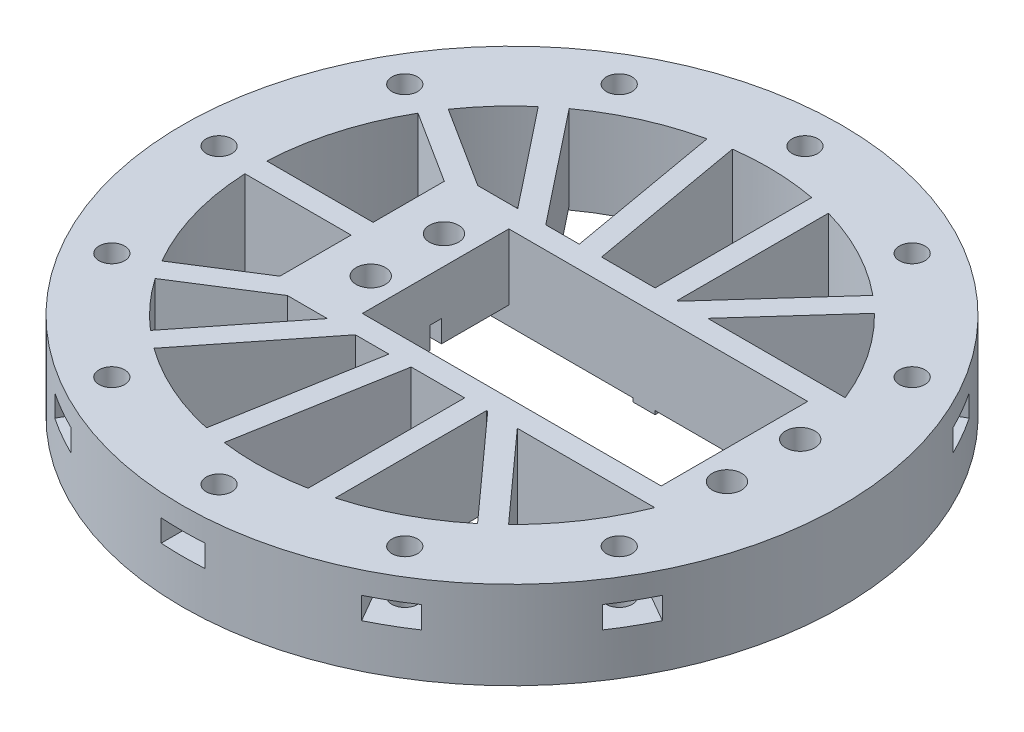
SolidWorks part; units mm, degrees
ref_plane "Front Plane" through (0, 0, 0) normal (0, 0, 1) x (1, 0, 0)
ref_plane "Top Plane" through (0, 0, 0) normal (0, 1, 0) x (1, 0, 0)
ref_plane "Right Plane" through (0, 0, 0) normal (1, 0, 0) x (0, 0, -1)
sketch "Sketch1" plane through (0, 0, 0) normal (0, 1, 0) x (1, 0, 0)
  line L0 (-43.0464, 0) -> (41.9462, 0) construction
  line L1 (0, 43.1152) -> (0, -41.8775) construction
  circle A1 centre (0, 0) radius 45
  dimension "D2" = 90
extrude "Boss-Extrude1" add sketch "Sketch1" along normal blind 12
sketch "Sketch2" plane through (0, 0, 0) normal (0, -1, 0) x (1, 0, 0)
  circle A0 centre (0, 0) radius 35
  dimension "D1" = 70
extrude "Cut-Extrude1" cut sketch "Sketch2" against normal blind 0.5
sketch "Sketch3" plane through (0, 0.5, 0) normal (0, -1, 0) x (1, 0, 0)
  line L0 (35, 0) -> (-35, 0) construction
  line L1 (0, -35) -> (0, 35) construction
  line L3 (37.5324, -10) -> (-17.4676, -10)
  line L4 (37.5324, -10) -> (37.5324, 10)
  line L5 (37.5324, 10) -> (-17.4676, 10)
  line L6 (-17.4676, -10) -> (-17.4676, 10)
  circle A0 centre (0, 0) radius 35 construction
  circle A1 centre (0, 0) radius 35 construction
  dimension "D1" = 20
  dimension "D2" = 55
  dimension "D3" = 10
  dimension "D4" = 37.5324
extrude "Cut-Extrude2" cut sketch "Sketch3" against normal blind 2.5 and the other way up to next
sketch "Sketch4" plane through (0, 3, 0) normal (0, -1, 0) x (1, 0, 0)
  line L0 (37.5324, 0) -> (-17.4676, 0) construction
  line L1 (37.5324, 10) -> (37.5324, -10) construction
  line L2 (-17.4676, 10) -> (-17.4676, -10) construction
  line L3 (0, -10) -> (0, 10) construction
  line L4 (-17.4676, -10) -> (33.541, -10) construction
  line L5 (33.541, 10) -> (-17.4676, 10) construction
  line L7 (30.3722, -10) -> (-10.4278, -10)
  line L8 (30.3722, -10) -> (30.3722, 10)
  line L9 (30.3722, 10) -> (-10.4278, 10)
  line L10 (-10.4278, -10) -> (-10.4278, 10)
  dimension "D1" = 20
  dimension "D2" = 40.8
  dimension "D3" = 30.3722
  dimension "D4" = 10
extrude "Cut-Extrude3" cut sketch "Sketch4" against normal blind 9
sketch "Sketch8" plane through (0, 0.5, 0) normal (0, -1, 0) x (1, 0, 0)
  line L0 (-17.4676, 0) -> (-35, 0) construction
  line L1 (-17.4676, 10) -> (-17.4676, -10) construction
  line L2 (8.0367, 10) -> (8.0367, 34.0648) construction
  line L3 (33.541, 10) -> (-17.4676, 10) construction
  line L4 (8.0367, -10) -> (8.0367, -29.3194) construction
  line L5 (-17.4676, -10) -> (33.541, -10) construction
  line L6 (6.5367, 10) -> (6.5367, 34.3842)
  line L7 (9.5367, 10) -> (9.5367, 33.6757)
  line L8 (9.5367, 10) -> (6.5367, 10)
  line L9 (9.5367, -10) -> (6.5367, -10)
  line L10 (6.5367, -10) -> (6.5367, -34.3842)
  line L11 (9.5367, -10) -> (9.5367, -33.6757)
  line L12 (-17.4676, 1.5) -> (-34.9678, 1.5)
  line L13 (-17.4676, -1.5) -> (-34.9678, -1.5)
  line L14 (-17.4676, 1.5) -> (-17.4676, -1.5)
  arc A0 (33.541, 10) -> (33.541, -10) centre (0, 0) ccw construction
  arc A1 (9.5367, 33.6757) -> (6.5367, 34.3842) centre (7.9531, 33.6757) ccw
  arc A2 (9.5367, -33.6757) -> (6.5367, -34.3842) centre (7.9531, -33.6757) cw
  arc A3 (-34.9678, 1.5) -> (-34.9678, -1.5) centre (-34.9678, 0) ccw
  dimension "D3" = 1.5
  dimension "D1" = 1.5
  dimension "D2" = 1.5
  dimension "D4" = 1.5
extrude "Boss-Extrude2" add sketch "Sketch8" along normal through all
sketch "Sketch15" plane through (0, 0, -1.5) normal (0, 0, -1) x (-1, 0, 0)
  line L0 (34.9678, 0) -> (17.4676, 0.5)
  line L1 (17.4676, 0.5) -> (17.4676, 0)
  line L3 (17.4676, 0) -> (34.9678, 0)
sketch "Sketch16" plane through (0, 3, 0) normal (0, -1, 0) x (1, 0, 0)
  line L0 (-17.4676, 0) -> (37.5324, 0) construction
  line L1 (-17.4676, 10) -> (-17.4676, -10) construction
  line L2 (37.5324, -10) -> (37.5324, 10) construction
  line L3 (30.3722, -0.8) -> (37.5324, -0.8)
  line L4 (-10.4278, -0.8) -> (-17.4676, -0.8)
  line L5 (-10.4278, 10) -> (-10.4278, -10) construction
  line L6 (-10.4278, 0.8) -> (-17.4676, 0.8)
  line L7 (-17.4676, 0.8) -> (-17.4676, -0.8)
  line L8 (-10.4278, 0.8) -> (-10.4278, -0.8)
  line L9 (30.3722, -10) -> (30.3722, 10) construction
  line L10 (30.3722, 0.8) -> (37.5324, 0.8)
  line L11 (37.5324, 0.8) -> (37.5324, -0.8)
  line L12 (30.3722, 0.8) -> (30.3722, -0.8)
  dimension "D1" = 0.8
extrude "Cut-Extrude10" cut sketch "Sketch16" against normal blind 3
sketch "Sketch27" plane through (0, 0, 0) normal (0, -1, 0) x (1, 0, 0)
  line L0 (0, 0) -> (0, -53.17) construction
  line L1 (0, 0) -> (47.7582, -27.5732) construction
  line L3 (31.641, -18.2679) -> (31.641, -21.7321) construction
  line L4 (31.641, -21.7321) -> (34.641, -23.4641) construction
  line L5 (34.641, -23.4641) -> (37.641, -21.7321) construction
  line L6 (37.641, -21.7321) -> (37.641, -18.2679) construction
  line L7 (37.641, -18.2679) -> (34.641, -16.5359) construction
  line L8 (34.641, -16.5359) -> (31.641, -18.2679) construction
  circle A0 centre (0, 0) radius 40 construction
  circle A1 centre (34.641, -20) radius 1.75
  circle A2 centre (0, 0) radius 35 construction
  circle A3 centre (34.641, -20) radius 3 construction
  circle A4 centre (20, -34.641) radius 1.75
  circle A5 centre (0, -40) radius 1.75
  circle A6 centre (-20, -34.641) radius 1.75
  circle A7 centre (-34.641, -20) radius 1.75
  circle A8 centre (-40, 0) radius 1.75
  circle A9 centre (-34.641, 20) radius 1.75
  circle A10 centre (-20, 34.641) radius 1.75
  circle A11 centre (0, 40) radius 1.75
  circle A12 centre (20, 34.641) radius 1.75
  circle A13 centre (34.641, 20) radius 1.75
  circle A15 centre (40, 0) radius 1.75 [skipped]
  point P28 (0, 0)
  point P41 (0, 0)
  dimension "D1" = 80
  dimension "D3" = 3.5
  dimension "D4" = 70
  dimension "D5" = 6
  dimension "D6" = 12
  dimension "D2" = 60
extrude "Cut-Extrude15" cut sketch "Sketch27" against normal through all
ref_plane "Plane1" through (0, 9, 0) normal (0, 1, 0) x (1, 0, 0)
sketch "Sketch28" plane through (0, 9, 0) normal (0, 1, 0) x (1, 0, 0)
  line L0 (0, 0) -> (-54.493, 0) construction
  line L1 (-31.641, 18.2679) -> (-31.641, 21.7321)
  line L2 (-36.5359, 0) -> (-38.2679, 3)
  line L3 (-38.2679, 3) -> (-44.8999, 3)
  line L4 (-31.641, 21.7321) -> (-37.3844, 25.048)
  line L5 (-40.3844, 19.8519) -> (-34.641, 16.5359)
  line L6 (-44.8999, -3) -> (-38.2679, -3)
  line L7 (-38.2679, -3) -> (-36.5359, 0)
  line L8 (-43.4641, 0) -> (-42.5981, -1.5) [skipped]
  line L9 (-41.7321, 3) -> (-42.5981, 1.5) [skipped]
  line L10 (-34.641, 16.5359) -> (-31.641, 18.2679)
  line L11 (-18.2679, 31.641) -> (-16.5359, 34.641)
  line L12 (-16.5359, 34.641) -> (-19.8519, 40.3844)
  line L13 (-25.048, 37.3844) -> (-21.7321, 31.641)
  line L14 (-21.7321, 31.641) -> (-18.2679, 31.641)
  line L15 (0, 36.5359) -> (3, 38.2679)
  line L16 (3, 38.2679) -> (3, 44.8999)
  line L17 (-3, 44.8999) -> (-3, 38.2679)
  line L18 (-3, 38.2679) -> (0, 36.5359)
  line L19 (18.2679, 31.641) -> (21.7321, 31.641)
  line L20 (21.7321, 31.641) -> (25.048, 37.3844)
  line L21 (19.8519, 40.3844) -> (16.5359, 34.641)
  line L22 (16.5359, 34.641) -> (18.2679, 31.641)
  line L23 (31.641, 18.2679) -> (34.641, 16.5359)
  line L24 (34.641, 16.5359) -> (40.3844, 19.8519)
  line L25 (37.3844, 25.048) -> (31.641, 21.7321)
  line L26 (31.641, 21.7321) -> (31.641, 18.2679)
  line L31 (31.641, -18.2679) -> (31.641, -21.7321)
  line L32 (31.641, -21.7321) -> (37.3844, -25.048)
  line L33 (40.3844, -19.8519) -> (34.641, -16.5359)
  line L34 (34.641, -16.5359) -> (31.641, -18.2679)
  line L35 (18.2679, -31.641) -> (16.5359, -34.641)
  line L36 (16.5359, -34.641) -> (19.8519, -40.3844)
  line L37 (25.048, -37.3844) -> (21.7321, -31.641)
  line L38 (21.7321, -31.641) -> (18.2679, -31.641)
  line L39 (0, -36.5359) -> (-3, -38.2679)
  line L40 (-3, -38.2679) -> (-3, -44.8999)
  line L41 (3, -44.8999) -> (3, -38.2679)
  line L42 (3, -38.2679) -> (0, -36.5359)
  line L43 (-18.2679, -31.641) -> (-21.7321, -31.641)
  line L44 (-21.7321, -31.641) -> (-25.048, -37.3844)
  line L45 (-19.8519, -40.3844) -> (-16.5359, -34.641)
  line L46 (-16.5359, -34.641) -> (-18.2679, -31.641)
  line L47 (-31.641, -18.2679) -> (-34.641, -16.5359)
  line L48 (-34.641, -16.5359) -> (-40.3844, -19.8519)
  line L49 (-37.3844, -25.048) -> (-31.641, -21.7321)
  line L50 (-31.641, -21.7321) -> (-31.641, -18.2679)
  line L51 (36.5359, 0) -> (38.2679, -3) [skipped]
  line L52 (38.2679, -3) -> (44.8999, -3) [skipped]
  line L53 (44.8999, 3) -> (38.2679, 3) [skipped]
  line L54 (38.2679, 3) -> (36.5359, 0) [skipped]
  arc A0 (-44.8999, 3) -> (-44.8999, -3) centre (0, 0) ccw
  circle A1 centre (-40, 0) radius 3 construction
  arc A2 (-37.3844, 25.048) -> (-40.3844, 19.8519) centre (0, 0) ccw
  circle A3 centre (-34.641, 20) radius 3 construction
  arc A4 (-19.8519, 40.3844) -> (-25.048, 37.3844) centre (0, 0) ccw
  circle A5 centre (-20, 34.641) radius 3 construction
  arc A6 (3, 44.8999) -> (-3, 44.8999) centre (0, 0) ccw
  circle A7 centre (0, 40) radius 3 construction
  arc A8 (25.048, 37.3844) -> (19.8519, 40.3844) centre (0, 0) ccw
  circle A9 centre (20, 34.641) radius 3 construction
  arc A10 (40.3844, 19.8519) -> (37.3844, 25.048) centre (0, 0) ccw
  circle A11 centre (34.641, 20) radius 3 construction
  arc A14 (37.3844, -25.048) -> (40.3844, -19.8519) centre (0, 0) ccw
  circle A15 centre (34.641, -20) radius 3 construction
  arc A16 (19.8519, -40.3844) -> (25.048, -37.3844) centre (0, 0) ccw
  circle A17 centre (20, -34.641) radius 3 construction
  arc A18 (-3, -44.8999) -> (3, -44.8999) centre (0, 0) ccw
  circle A19 centre (0, -40) radius 3 construction
  arc A20 (-25.048, -37.3844) -> (-19.8519, -40.3844) centre (0, 0) ccw
  circle A21 centre (-20, -34.641) radius 3 construction
  arc A22 (-40.3844, -19.8519) -> (-37.3844, -25.048) centre (0, 0) ccw
  circle A23 centre (-34.641, -20) radius 3 construction
  arc A24 (44.8999, -3) -> (44.8999, 3) centre (0, 0) ccw [skipped]
  circle A25 centre (40, 0) radius 3 construction
  point P94 (0, 0)
  dimension "D1" = 90
  dimension "D2" = 6
  dimension "D3" = 12
extrude "Cut-Extrude17" cut sketch "Sketch28" against normal blind 3
sketch "Sketch29" plane through (0, 0.5, 0) normal (0, -1, 0) x (1, 0, 0)
  line L0 (32.4962, -13) -> (13.7255, -13)
  line L1 (9.5367, -33.6757) -> (9.5367, -10) construction
  line L2 (9.5367, -13) -> (9.5367, -33.6757)
  line L3 (9.5367, -10) -> (33.541, -10) construction
  line L4 (6.5367, -13) -> (-0.7691, -13)
  line L5 (6.5367, -10) -> (6.5367, -34.3842) construction
  line L6 (-20.4676, -11.223) -> (-20.4676, -1.5)
  line L7 (-34.9678, -1.5) -> (-17.4676, -1.5) construction
  line L8 (-20.4676, -1.5) -> (-34.9678, -1.5)
  line L9 (-17.4676, -0.8) -> (-17.4676, -10) construction
  line L10 (32.4962, 13) -> (13.7255, 13)
  line L11 (9.5367, 10) -> (9.5367, 33.6757) construction
  line L12 (9.5367, 13) -> (9.5367, 33.6757)
  line L13 (-7.5493, 34.1761) -> (-3.8154, 13)
  line L14 (6.5367, 13) -> (-0.7691, 13)
  line L15 (6.5367, 34.3842) -> (6.5367, 10) construction
  line L16 (-20.4676, 11.223) -> (-20.4676, 1.5)
  line L17 (-17.4676, 1.5) -> (-34.9678, 1.5) construction
  line L18 (-20.4676, 1.5) -> (-34.9678, 1.5)
  line L19 (6.5367, 13) -> (6.5367, 34.3842)
  line L20 (6.5367, -34.3842) -> (6.5367, -13)
  line L21 (0, 0) -> (-21.7353, -27.4331) construction
  line L22 (-20.5397, -28.3394) -> (-8.3862, -13)
  line L23 (-22.8911, -26.4764) -> (-12.2137, -13)
  line L24 (0, 0) -> (-20.4676, -13) construction
  line L25 (-17.6698, -13) -> (-28.713, -20.0141)
  line L26 (-20.4676, -11.223) -> (-30.3215, -17.4817)
  line L27 (0, 0) -> (-35, 0) construction
  line L28 (-20.4676, 11.223) -> (-30.3215, 17.4817)
  line L29 (-17.6698, 13) -> (-28.713, 20.0141)
  line L30 (-22.8911, 26.4764) -> (-12.2137, 13)
  line L31 (-20.5397, 28.3394) -> (-8.3862, 13)
  line L32 (-12.2137, 13) -> (-17.6698, 13)
  line L33 (0, 0) -> (-6.0777, -34.4683) construction
  line L34 (-4.5949, -34.6971) -> (-0.7691, -13)
  line L35 (-7.5493, -34.1761) -> (-3.8154, -13)
  line L36 (-3.8154, -13) -> (-17.6698, -13)
  line L37 (-4.5949, 34.6971) -> (-0.7691, 13)
  line L38 (-3.8154, 13) -> (-8.3862, 13)
  line L39 (0, 0) -> (23.4214, -26.0084) construction
  line L40 (9.6883, -13) -> (22.2852, -26.9883)
  line L41 (13.7255, -13) -> (24.5145, -24.9808)
  line L42 (13.7255, 13) -> (24.5145, 24.9808)
  line L43 (9.6883, 13) -> (22.2852, 26.9883)
  line L44 (9.6883, -13) -> (9.5367, -13)
  line L45 (9.6883, 13) -> (9.5367, 13)
  arc A0 (9.5367, -33.6757) -> (22.2852, -26.9883) centre (0, 0) ccw
  arc A1 (6.5367, 34.3842) -> (-4.5949, 34.6971) centre (0, 0) ccw
  arc A2 (32.4962, 13) -> (24.5145, 24.9808) centre (0, 0) ccw
  arc A3 (-34.9678, -1.5) -> (-30.3215, -17.4817) centre (0, 0) ccw
  circle A4 centre (0, 0) radius 35 construction
  arc A5 (-7.5493, 34.1761) -> (-20.5397, 28.3394) centre (0, 0) ccw
  arc A6 (-4.5949, -34.6971) -> (6.5367, -34.3842) centre (0, 0) ccw
  arc A7 (-20.5397, -28.3394) -> (-7.5493, -34.1761) centre (0, 0) ccw
  arc A8 (-28.713, -20.0141) -> (-22.8911, -26.4764) centre (0, 0) ccw
  arc A9 (-30.3215, 17.4817) -> (-34.9678, 1.5) centre (0, 0) ccw
  arc A10 (-22.8911, 26.4764) -> (-28.713, 20.0141) centre (0, 0) ccw
  arc A11 (24.5145, -24.9808) -> (32.4962, -13) centre (0, 0) ccw
  arc A12 (22.2852, 26.9883) -> (9.5367, 33.6757) centre (0, 0) ccw
  point P11 (21.5389, -10)
  point P23 (-17.4676, -5.4)
  line M3 (-17.4676, -1.5) -> (-34.9678, -1.5)
  arc M4 (-34.9678, -1.5) -> (6.5367, -34.3842) centre (0, 0) ccw
  line M5 (6.5367, -34.3842) -> (6.5367, -10)
  dimension "D1" = 1.5
  dimension "D2" = 3
  dimension "D3" = 3
  dimension "D4" = 80
  dimension "D5" = 1.5
  dimension "D6" = 1.5
  dimension "D7" = 1.5
sketch "Sketch32" plane through (0, 3, 0) normal (0, -1, 0) x (1, 0, 0)
  line L0 (-17.4676, 0) -> (37.5324, 0) construction
  line L1 (-17.4676, -1.5) -> (-17.4676, 1.5) construction
  line L2 (37.5324, 10) -> (37.5324, -10) construction
  line L3 (10.0324, 0) -> (10.0324, -10) construction
  line L6 (9.5367, -10) -> (33.541, -10) construction
  circle A0 centre (-14.2876, -5) radius 2
  circle A1 centre (-14.2876, 5) radius 2
  circle A2 centre (34.3524, -5) radius 2
  circle A3 centre (34.3524, 5) radius 2
  dimension "D1" = 24.32
  dimension "D3" = 4
  dimension "D2" = 5
extrude "Cut-Extrude21" cut sketch "Sketch32" against normal through all
extrude "Cut-Extrude22" cut sketch "Sketch29" against normal blind 12 contours L28 A9 L18 L16 | L26 L6 M3 M4 | L23 L36 L25 M4 | L35 L36 L22 M4 | L34 L4 M4 M5 | L2 A0 L40 L44 | L41 A11 L0 | L10 A2 L42 | L43 A12 L12 L45 | L19 A1 L37 L14 | L13 A5 L31 L38 | L30 A10 L29 L32 region at (23.89, 0.5, -17.1237) region at (13.9029, 0.5, -24.813) region at (1.8383, 0.5, -24.6789) region at (-27.5459, 0.5, -7.8919) region at (-10.8152, 0.5, -24.1049) region at (-20.9968, 0.5, -18.9781) region at (23.89, 0.5, 17.1237) region at (13.9029, 0.5, 24.813) region at (-10.8152, 0.5, 24.1049) region at (1.8383, 0.5, 24.6789) region at (-27.5459, 0.5, 7.8919) region at (-20.9968, 0.5, 18.9781)
